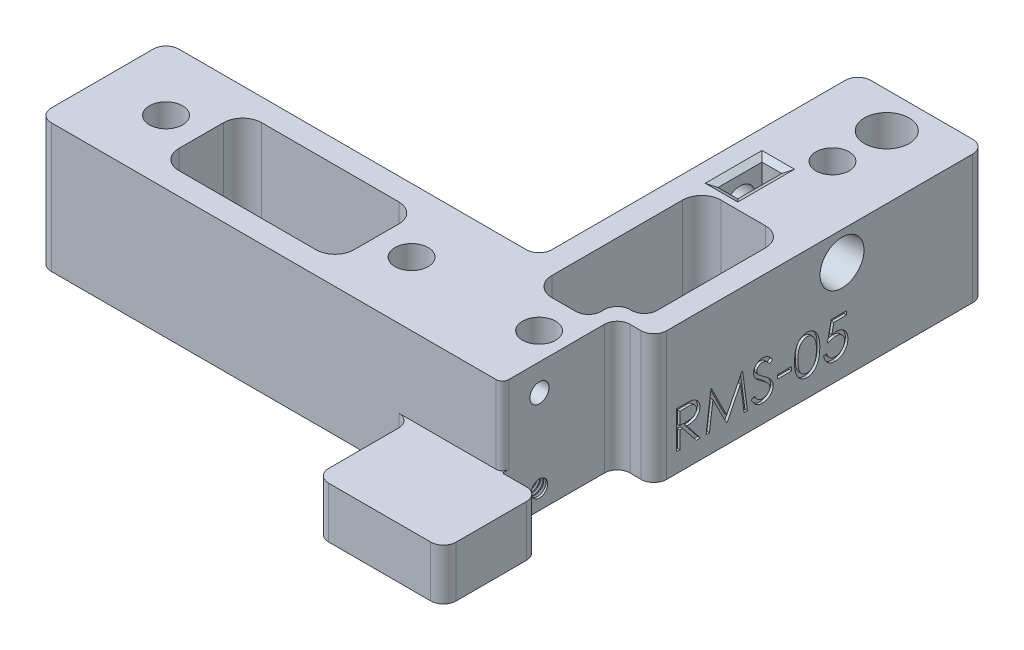
SolidWorks part; units mm, degrees
ref_plane "Front" through (0, 0, 0) normal (0, 0, 1) x (1, 0, 0)
ref_plane "Top" through (0, 0, 0) normal (0, 1, 0) x (1, 0, 0)
ref_plane "Right" through (0, 0, 0) normal (1, 0, 0) x (0, 0, -1)
sketch "Sketch1" plane through (0, 0, 0) normal (0, 1, 0) x (1, 0, 0)
  line L0 (0, 0) -> (78.5, 0)
  line L1 (78.5, 0) -> (78.5, 20)
  line L2 (78.5, 20) -> (20, 20)
  line L3 (20, 20) -> (20, 70)
  line L4 (20, 70) -> (0, 70)
  line L5 (0, 70) -> (0, 0)
  line L6 (78.5, 10) -> (0, 10) construction
  line L7 (10, 70) -> (10, 0) construction
  circle A0 centre (10, 56) radius 2.6
  circle A1 centre (68.5, 10) radius 2.6
  circle A2 centre (10, 10) radius 2.6
  circle A3 centre (30, 10) radius 2.6
  dimension "D5" = 5.2
  dimension "D6" = 10
  dimension "D7" = 20
  dimension "D1" = 78.5
  dimension "D2" = 70
  dimension "D3" = 14
  dimension "D4" = 20
extrude "Boss-Extrude1" add sketch "Sketch1" along normal blind 10
sketch "Sketch4" plane through (0, 0, 0) normal (-1, 0, 0) x (0, 0, 1)
  line L0 (-70, 10) -> (-70, 0) construction
  line L1 (-70, 10) -> (0, 10) construction
  circle A0 centre (-47.5, 5.5) radius 2.4
  dimension "D1" = 22.5
  dimension "D2" = 4.5
  dimension "D3" = 4.8
extrude "motor tensioning hole" cut sketch "Sketch4" against normal through all
sketch "Sketch10" plane through (0, 10, 0) normal (0, 1, 0) x (1, 0, 0)
  line L0 (20, 20) -> (20, 70) construction
  line L1 (0, 0) -> (20, 0)
  line L2 (0, 0) -> (0, -15)
  line L3 (0, -15) -> (20, -15)
  line L4 (20, 0) -> (20, -15)
  dimension "D1" = 15
extrude "Boss-Extrude3" add sketch "Sketch10" against normal blind 10
fillet "Fillet1" radius 2 8 edges at (0, 5, -70) (20, 5, -70) (20, 5, -20) (78.5, 5, 0) (78.5, 5, -20) (20, 5, 15) (20, 5, 0) (0, 5, 15)
chamfer "Chamfer2" distance 12 angle 5 1 edges at (0, 5.5, -45.1) first distance on face at (0, 5.5, -45.1)
sketch "Sketch17" plane through (20, 0, 0) normal (1, 0, 0) x (0, 0, -1)
  line L0 (44.05, 7.4919) -> (44.05, 10)
  line L1 (44.05, 3.5081) -> (47.5, 1.5163)
  line L2 (47.5, 1.5163) -> (50.95, 3.5081)
  line L3 (50.95, 3.5081) -> (50.95, 7.4919)
  line L4 (50.95, 7.4919) -> (47.5, 9.4837) construction
  line L5 (47.5, 9.4837) -> (44.05, 7.4919) construction
  line L6 (44.05, 7.4919) -> (44.05, 3.5081)
  line L7 (22, 10) -> (68, 10) construction
  line L8 (44.05, 10) -> (50.95, 10)
  line L9 (50.95, 10) -> (50.95, 7.4919)
  circle A0 centre (47.5, 5.5) radius 3.45 construction
  dimension "D1" = 6.9
extrude "Cut-Extrude8" cut sketch "Sketch17" against normal blind 3.1 from offset 4 offset against normal yes
chamfer "Chamfer3" distance 1 angle 30 4 edges at (14.45, 10, -44.05) (16, 10, -47.5) (14.45, 10, -50.95) (12.9, 10, -47.5) first distance on face at (10, 10, -7.4)
sketch "Sketch6" plane through (0, 10, 0) normal (0, 1, 0) x (1, 0, 0)
  line L0 (18, 70) -> (2, 70) construction
  line L1 (0, 68) -> (0, -13) construction
  circle A0 centre (9.8995, 64.4167) radius 3.5
  dimension "D1" = 5.5833
  dimension "D2" = 7
  dimension "D3" = 9.8995
extrude "M3 Screwhead Clearance" cut sketch "Sketch6" against normal through all
sketch "Sketch15" [suppressed] plane through (0, 10, 0) normal (0, 1, 0) x (1, 0, 0)
  line L0 (10, 56) -> (10, 63) construction
  line L1 (7.4, 56) -> (7.4, 63)
  line L2 (12.6, 56) -> (12.6, 63)
  line L3 (18, 70) -> (2, 70) construction
  line L4 (30, 10) -> (24.5, 10) construction
  line L7 (30, 7.4) -> (24.5, 7.4)
  line L8 (30, 12.6) -> (24.5, 12.6)
  arc A0 (7.4, 56) -> (12.6, 56) centre (10, 56) ccw
  arc A1 (12.6, 63) -> (7.4, 63) centre (10, 63) ccw
  circle A2 centre (10, 56) radius 2.6 construction
  arc A6 (30, 7.4) -> (30, 12.6) centre (30, 10) ccw
  arc A7 (24.5, 12.6) -> (24.5, 7.4) centre (24.5, 10) ccw
  circle A8 centre (10, 10) radius 2.6 construction
  circle A9 centre (30, 10) radius 2.6 construction
  point P3 (10, 59.5)
  point P15 (27.25, 10)
  dimension "D2" = 14.5
  dimension "D1" = 7
extrude "M5 Slots for Alternate Plate" [suppressed] cut sketch "Sketch15" against normal through all
mirror "Mirror1" about plane through (78.5, 10, 0) normal (-1, 0, 0) of bodies 109 101
delete or keep bodies "Body-Delete/Keep 1" type delete bodies bodies 109
sketch "Sketch2" plane through (0, 0, 0) normal (0, 1, 0) x (1, 0, 0)
  line L6 (157, -13) -> (157, 68)
  line L7 (155, 70) -> (139, 70)
  line L8 (137, 68) -> (137, 22)
  line L9 (135, 20) -> (80.5, 20)
  line L10 (78.5, 18) -> (78.5, 2)
  line L11 (80.5, 0) -> (135, 0)
  line L12 (157, -13) -> (157, 68)
  line L13 (155, 70) -> (139, 70)
  line L14 (137, 68) -> (137, 22)
  line L15 (135, 20) -> (80.5, 20)
  line L16 (78.5, 18) -> (78.5, 2)
  line L17 (80.5, 0) -> (135, 0)
  line L20 (139, -15) -> (155, -15)
  line L21 (139, -15) -> (155, -15)
  line L22 (137, -2) -> (137, -13)
  line L23 (137, -2) -> (137, -13)
  circle A0 centre (147, 56) radius 2.6 construction
  circle A1 centre (147, 10) radius 2.6 construction
  circle A2 centre (88.5, 10) radius 2.6 construction
  circle A4 centre (147, 10) radius 2.6
  circle A5 centre (88.5, 10) radius 2.6
  circle A6 centre (127, 10) radius 2.6 construction
  arc A14 (157, 68) -> (155, 70) centre (155, 68) ccw
  arc A15 (157, 68) -> (155, 70) centre (155, 68) ccw
  arc A16 (139, 70) -> (137, 68) centre (139, 68) ccw
  arc A17 (139, 70) -> (137, 68) centre (139, 68) ccw
  arc A18 (135, 20) -> (137, 22) centre (135, 22) ccw
  arc A19 (135, 20) -> (137, 22) centre (135, 22) ccw
  arc A20 (80.5, 20) -> (78.5, 18) centre (80.5, 18) ccw
  arc A21 (80.5, 20) -> (78.5, 18) centre (80.5, 18) ccw
  arc A22 (78.5, 2) -> (80.5, 0) centre (80.5, 2) ccw
  arc A23 (78.5, 2) -> (80.5, 0) centre (80.5, 2) ccw
  arc A24 (155, -15) -> (157, -13) centre (155, -13) ccw
  arc A28 (155, -15) -> (157, -13) centre (155, -13) ccw
  arc A29 (137, -2) -> (135, 0) centre (135, -2) ccw
  arc A30 (137, -2) -> (135, 0) centre (135, -2) ccw
  arc A31 (137, -13) -> (139, -15) centre (139, -13) ccw
  arc A32 (137, -13) -> (139, -15) centre (139, -13) ccw
  circle A33 centre (147, 56) radius 2.6
  circle A34 centre (127, 10) radius 2.6
  dimension "D1" = 0
extrude "height bump" add sketch "Sketch2" against normal blind 10.2
sketch "Sketch16" [suppressed] plane through (0, 0, 0) normal (0, 1, 0) x (1, 0, 0)
  line L0 (132.5, 7.4) -> (127, 7.4) construction
  line L1 (127, 12.6) -> (132.5, 12.6) construction
  line L2 (144.4, 56) -> (144.4, 63) construction
  line L3 (149.6, 63) -> (149.6, 56) construction
  line L4 (132.5, 7.4) -> (127, 7.4)
  line L5 (127, 12.6) -> (132.5, 12.6)
  line L6 (144.4, 56) -> (144.4, 63)
  line L7 (149.6, 63) -> (149.6, 56)
  arc A0 (127, 12.6) -> (127, 7.4) centre (127, 10) ccw construction
  arc A1 (132.5, 7.4) -> (132.5, 12.6) centre (132.5, 10) ccw construction
  arc A2 (144.4, 56) -> (149.6, 56) centre (147, 56) ccw construction
  arc A3 (149.6, 63) -> (144.4, 63) centre (147, 63) ccw construction
  arc A4 (127, 12.6) -> (127, 7.4) centre (127, 10) ccw
  arc A5 (132.5, 7.4) -> (132.5, 12.6) centre (132.5, 10) ccw
  arc A6 (144.4, 56) -> (149.6, 56) centre (147, 56) ccw
  arc A7 (149.6, 63) -> (144.4, 63) centre (147, 63) ccw
extrude "slotted height bump cutout" [suppressed] cut sketch "Sketch16" against normal through all
sketch "Sketch12" plane through (157, 0, 0) normal (1, 0, 0) x (0, 0, -1)
  line L1 (-13, -10.2) -> (68, -10.2) construction
  line L2 (0, 10) -> (18, 10)
  line L3 (0, 10) -> (0, -10.2)
  line L4 (0, -10.2) -> (18, -10.2)
  line L5 (18, 10) -> (18, -10.2)
  dimension "D2" = 18
extrude "Limit Switch Cutout" cut sketch "Sketch12" against normal blind 5.75
sketch "Sketch3" plane through (151.25, 0, 0) normal (1, 0, 0) x (0, 0, -1)
  line L0 (70, 10) -> (0, 10) construction
  line L2 (-1.8564, 10) -> (11.9064, 10) construction
  line L3 (70, -10.2) -> (0, -10.2) construction
  line L4 (5.8, -7.2) -> (5.8, 5.8) construction
  line L5 (2.8, -10.2) -> (2.8, 10) construction
  line L7 (68, 10) -> (18, 10) construction
  circle A2 centre (5.8, 5.8) radius 1.5
  circle A3 centre (5.8, -7.2) radius 1.3
  dimension "D1" = 2.6
  dimension "D2" = 3
  dimension "D3" = 13
  dimension "D4" = 4.2
  dimension "D6" = 2.8
  dimension "D7" = 3
extrude "d2hw limit switch holes" cut sketch "Sketch3" against normal blind 7
chamfer "Chamfer1" [suppressed] distance 0.4 angle 75
sketch "Sketch9" [suppressed] plane through (0, 0, 0) normal (-1, 0, 0) x (0, 0, 1)
  line L0 (13, 2) -> (-44.0501, 2) construction
  line L1 (13, 0) -> (13, 10) construction
  line L2 (-44.0501, 2) -> (-44.0501, 5.5) construction
  line L3 (-68, 0) -> (13, 0) construction
  circle A0 centre (-47.5, 5.5) radius 3.4499 construction
  text T0 "LMS-04" font "Century Gothic" height in points 22
  dimension "D1" = 2
extrude "Cut-Extrude3" [suppressed] cut sketch "Sketch9" against normal blind 0.4
sketch "Sketch8" plane through (157, 0, 0) normal (1, 0, 0) x (0, 0, -1)
  line L0 (-0.4035, -7.2) -> (70, -7.2) construction
  line L2 (70, -10.2) -> (70, 10) construction
  line L3 (18, -10.2) -> (68, -10.2) construction
  text T0 "RMS-05" font "Century Gothic" height in points 22
  dimension "D1" = 3
extrude "Right Side Part Num Short" cut sketch "Sketch8" against normal blind 0.4
sketch "Sketch11" plane through (0, 10, 0) normal (0, 1, 0) x (1, 0, 0)
  line L0 (157, 68) -> (157, 18) construction
  line L1 (157, 0) -> (134.8301, 0)
  line L2 (157, 0) -> (157, -15)
  line L3 (157, -15) -> (134.8301, -15)
  line L4 (134.8301, 0) -> (134.8301, -15)
  line L7 (155, -15) -> (139, -15) construction
  line L8 (135, 0) -> (80.5, 0) construction
extrude "Cut-Extrude4" cut sketch "Sketch11" against normal offset from surface (12.2 mm away) 8 up to face at (127, -10.2, -7.4)
fillet "Fillet2" radius 2 3 edges at (151.25, -0.1, -18) (157, -0.1, -18) (157, -6.2, 0)
sketch "Sketch13" plane through (151.25, 0, 0) normal (1, 0, 0) x (0, 0, -1)
  line L0 (5.8, 5.05) -> (5.8, -2.95) construction
  line L1 (5.8, 5.05) -> (5.8, 10) construction
  line L2 (16, 10) -> (0, 10) construction
  line L3 (0, 10) -> (0, -2.2) construction
  line L4 (-13, -10.2) -> (-2, -10.2) construction
  circle A0 centre (5.8, 5.05) radius 1.3
  circle A1 centre (5.8, -2.95) radius 1.3
  dimension "D1" = 7.25
  dimension "D3" = 2.6
  dimension "D2" = 8
  dimension "D4" = 5.8
extrude "compact switch holes" [suppressed] cut sketch "Sketch13" against normal blind 6
fillet "Fillet3" radius 1 1 edges at (151.25, 3.9, 0)
sketch "Sketch14" [suppressed] plane through (0, 10, 0) normal (0, 1, 0) x (1, 0, 0)
  line L0 (2, -15) -> (18, -15) construction
  line L1 (0, -15) -> (22, -15)
  line L2 (0, -15) -> (0, 0)
  line L3 (0, 0) -> (22, 0)
  line L4 (22, -15) -> (22, 0)
extrude "Cut-Extrude7" [suppressed] cut sketch "Sketch14" against normal offset from surface (2 mm away) 8 up to face at (147.1005, 0, -60.9167)
fillet "Fillet4" [suppressed] radius 2
sketch "Sketch18" plane through (0, 10, 0) normal (0, 1, 0) x (1, 0, 0)
  line L0 (88.5, 10) -> (127, 10) construction
  line L1 (147, 10) -> (147, 47.5) construction
  line L2 (144.1, 47.5) -> (141, 47.5) construction
  line L3 (80.5, 20) -> (135, 20) construction
  line L4 (149.25, 15.5) -> (151.25, 15.5) construction
  line L6 (121.5, 3.5) -> (94, 3.5)
  line L7 (121.5, 3.5) -> (121.5, 16.5)
  line L8 (121.5, 16.5) -> (94, 16.5)
  line L9 (94, 3.5) -> (94, 16.5)
  line L10 (121.5, 3.5) -> (94, 16.5) construction
  line L11 (121.5, 16.5) -> (94, 3.5) construction
  line L12 (149.25, 15.5) -> (140.5, 15.5)
  line L13 (153.5, 20) -> (153.5, 42)
  line L14 (153.5, 42) -> (140.5, 42)
  line L15 (140.5, 15.5) -> (140.5, 42)
  line L16 (153.5, 15.5) -> (140.5, 42) construction
  line L17 (153.5, 42) -> (140.5, 15.5) construction
  line L20 (153.5, 20) -> (149.25, 20)
  line L21 (149.25, 15.5) -> (149.25, 20)
  line L22 (151.25, 16) -> (151.25, 1) construction
  line L23 (153.5, 20) -> (153.5, 18) construction
  line L24 (153.25, 18) -> (155, 18) construction
  circle A0 centre (127, 10) radius 2.6 construction
  circle A1 centre (88.5, 10) radius 2.6 construction
  point P10 (147, 28.75)
  point P11 (107.75, 10)
  dimension "D1" = 3.5
  dimension "D2" = 5.5
  dimension "D3" = 5.5
  dimension "D4" = 2
extrude "Cut-Extrude9" cut sketch "Sketch18" against normal through all
fillet "Fillet5" radius 3 7 edges at (121.5, -0.1, -3.5) (94, -0.1, -3.5) (94, -0.1, -16.5) (121.5, -0.1, -16.5) (140.5, -0.1, -15.5) (140.5, -0.1, -42) (153.5, -0.1, -42)
fillet "Fillet6" radius 2 3 edges at (153.5, -0.1, -20) (149.25, -0.1, -20) (149.25, -0.1, -15.5)
thread "Thread1" pitch 0.5 method cut profile "Thread Profile1" start angle 0, offset 0, length 0, pitch 0.5, diameter 2.6
ref_plane "Plane1" through (151.25, -7.2, -4.5) normal (0, -1, 0) x (0, 0, 1)
sketch "Thread Profile1" plane through (151.25, -7.2, -4.5) normal (0, -1, 0) x (0, 0, 1)
  line L0 (0, 0) -> (0, 0.5) construction
  line L1 (0, 0) -> (0.2706, 0.1562)
  line L2 (0.2706, 0.1562) -> (0.2706, 0.2187)
  line L3 (0.2706, 0.2187) -> (0, 0.375)
  line L4 (0.2706, 0.1875) -> (0, 0.1875) construction
  line L11 (0, 0) -> (0, 0.375)
  point P2 (0, 0)
  dimension "Pitch" = 0.5
  dimension "Profile_Angle" = 60
  dimension "Profile_Land" = 0.0625
  dimension "Profile_Height" = 0.2706
